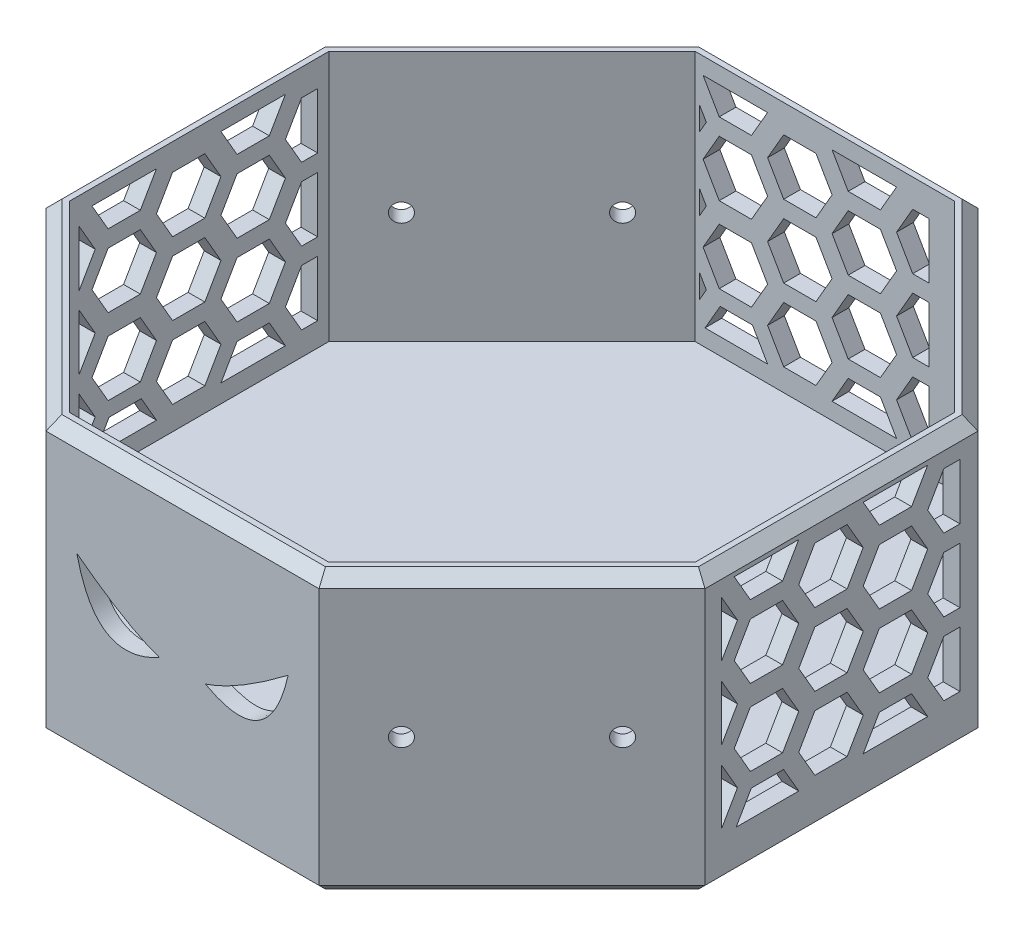
SolidWorks part; units mm, degrees
ref_plane "Plano frontal" through (0, 0, 0) normal (0, 0, 1) x (1, 0, 0)
ref_plane "Plano superior" through (0, 0, 0) normal (0, 1, 0) x (1, 0, 0)
ref_plane "Plano direito" through (0, 0, 0) normal (1, 0, 0) x (0, 0, -1)
sketch "Esboço1" plane through (0, 0, 0) normal (0, 1, 0) x (1, 0, 0)
  line L24 (59, -24.4386) -> (59, 24.4386)
  line L37 (24.4386, 59) -> (-24.4386, 59)
  line L38 (-24.4386, 59) -> (-59, 24.4386)
  line L39 (-59, 24.4386) -> (-59, -24.4386)
  line L40 (-59, -24.4386) -> (-24.4386, -59)
  line L41 (-24.4386, -59) -> (24.4386, -59)
  line L42 (24.4386, -59) -> (59, -24.4386)
  line L43 (59, 24.4386) -> (24.4386, 59)
  circle A0 centre (0, 0) radius 59 construction
  point P1 (-59, 0)
  dimension "D1" = 118
extrude "Ressalto-extrusão1" add sketch "Esboço1" along normal blind 50
sketch "Esboço2" plane through (0, 50, 0) normal (0, 1, 0) x (1, 0, 0)
  line L0 (59, 24.4386) -> (24.4386, 59) construction
  line L1 (56, 23.196) -> (23.196, 56)
  line L2 (23.196, 56) -> (-23.196, 56)
  line L3 (-23.196, 56) -> (-56, 23.196)
  line L4 (-56, 23.196) -> (-56, -23.196)
  line L5 (-56, -23.196) -> (-23.196, -56)
  line L6 (-23.196, -56) -> (23.196, -56)
  line L7 (23.196, -56) -> (56, -23.196)
  line L8 (56, -23.196) -> (56, 23.196)
  circle A0 centre (0, 0) radius 56 construction
  point P1 (-56, 0)
  dimension "D1" = 3
extrude "Corte-extrusão2" cut sketch "Esboço2" against normal blind 45
sketch "Esboço14" plane through (-41.7193, 0, 41.7193) normal (-0.7071, 0, 0.7071) x (0.7071, 0, 0.7071)
  line L0 (-14, 25) -> (14, 25) construction
  line L1 (-24.4386, 0) -> (24.4386, 0) construction
  circle A0 centre (-14, 25) radius 1.65
  circle A1 centre (14, 25) radius 1.65
  point P4 (0, 25)
  dimension "D3" = 3.3
  dimension "D1" = 28
  dimension "D2" = 25
extrude "Corte-extrusão6" cut sketch "Esboço14" against normal through all
sketch "Esboço15" plane through (-41.7193, 0, -41.7193) normal (-0.7071, 0, -0.7071) x (-0.7071, 0, 0.7071)
  line L0 (-14, 25) -> (14, 25) construction
  line L1 (-24.4386, 0) -> (24.4386, 0) construction
  circle A0 centre (-14, 25) radius 1.65
  circle A1 centre (14, 25) radius 1.65
  point P4 (0, 25)
  dimension "D1" = 3.3
  dimension "D2" = 28
  dimension "D3" = 25
extrude "Corte-extrusão7" cut sketch "Esboço15" against normal through all
chamfer "Chanfro1" distance 2 angle 45 16 edges at (-59, 0, 0) (-41.7193, 0, -41.7193) (0, 0, -59) (41.7193, 0, -41.7193) (59, 0, 0) (41.7193, 0, 41.7193) (0, 0, 59) (-41.7193, 0, 41.7193) (41.7193, 50, 41.7193) (59, 50, 0) (41.7193, 50, -41.7193) (0, 50, -59) (-41.7193, 50, -41.7193) (-59, 50, 0) (-41.7193, 50, 41.7193) (0, 50, 59)
sketch "Esboço11" plane through (-59, 0, 0) normal (-1, 0, 0) x (0, 0, 1)
  line L12 (18.862, 8.2396) -> (16.1485, 12.9395)
  line L15 (7.6615, 27.2396) -> (4.7748, 32.2396)
  line L53 (4.7748, 32.2396) -> (-0.9987, 32.2396)
  line L169 (-0.9987, 32.2396) -> (-3.8855, 27.2396)
  line L170 (16.1485, 12.9395) -> (10.375, 12.9395)
  line L171 (10.375, 12.9395) -> (7.6615, 8.2396)
  line L172 (-3.8855, 27.2396) -> (-0.9987, 22.2396)
  line L173 (-0.9987, 22.2396) -> (4.7748, 22.2396)
  line L174 (4.7748, 22.2396) -> (7.6615, 27.2396)
  line L175 (-3.8855, 21.2396) -> (-6.7722, 26.2396)
  line L176 (-6.7722, 26.2396) -> (-12.5457, 26.2396)
  line L177 (-12.5457, 26.2396) -> (-15.4325, 21.2396)
  line L178 (-15.4325, 21.2396) -> (-12.5457, 16.2396)
  line L179 (-12.5457, 16.2396) -> (-6.7722, 16.2396)
  line L180 (-6.7722, 16.2396) -> (-3.8855, 21.2396)
  line L181 (7.6615, 40.2396) -> (4.7748, 45.2396)
  line L182 (4.7748, 45.2396) -> (-0.9987, 45.2396)
  line L183 (-0.9987, 45.2396) -> (-3.8855, 40.2396)
  line L184 (-3.8855, 40.2396) -> (-0.9987, 35.2396)
  line L185 (-0.9987, 35.2396) -> (4.7748, 35.2396)
  line L186 (4.7748, 35.2396) -> (7.6615, 40.2396)
  line L187 (7.6615, 14.2396) -> (4.7748, 19.2396)
  line L188 (4.7748, 19.2396) -> (-0.9987, 19.2396)
  line L189 (-0.9987, 19.2396) -> (-3.8855, 14.2396)
  line L190 (-3.8855, 14.2396) -> (-0.9987, 9.2396)
  line L191 (-0.9987, 9.2396) -> (4.7748, 9.2396)
  line L192 (4.7748, 9.2396) -> (7.6615, 14.2396)
  line L193 (7.6615, 8.2396) -> (18.862, 8.2396)
  line L194 (-15.4325, 8.2396) -> (-3.8855, 8.2396)
  line L195 (-3.8855, 8.2396) -> (-6.7722, 13.2396)
  line L196 (-6.7722, 13.2396) -> (-12.5457, 13.2396)
  line L197 (-12.5457, 13.2396) -> (-15.4325, 8.2396)
  line L198 (-15.4325, 47.2396) -> (-3.8855, 47.2396)
  line L199 (-3.8855, 34.2396) -> (-6.7722, 39.2396)
  line L200 (-6.7722, 39.2396) -> (-12.5457, 39.2396)
  line L201 (-12.5457, 39.2396) -> (-15.4325, 34.2396)
  line L202 (-15.4325, 34.2396) -> (-12.5457, 29.2396)
  line L203 (-12.5457, 29.2396) -> (-6.7722, 29.2396)
  line L204 (-6.7722, 29.2396) -> (-3.8855, 34.2396)
  line L205 (-15.4325, 47.2396) -> (-12.5457, 42.2396)
  line L206 (-12.5457, 42.2396) -> (-6.7722, 42.2396)
  line L207 (-6.7722, 42.2396) -> (-3.8855, 47.2396)
  line L208 (-21.206, 45.2396) -> (-21.206, 9.2396) construction
  line L209 (-21.206, 45.2396) -> (-21.206, 35.2396)
  line L210 (-15.4325, 40.2396) -> (-18.3192, 45.2396)
  line L211 (-18.3192, 45.2396) -> (-21.206, 45.2396)
  line L212 (-21.206, 35.2396) -> (-18.3192, 35.2396)
  line L213 (-18.3192, 35.2396) -> (-15.4325, 40.2396)
  line L214 (-15.4325, 27.2396) -> (-18.3192, 32.2396)
  line L215 (-18.3192, 32.2396) -> (-21.206, 32.2396)
  line L216 (-21.206, 32.2396) -> (-21.206, 22.2396)
  line L217 (-21.206, 22.2396) -> (-18.3192, 22.2396)
  line L218 (-18.3192, 22.2396) -> (-15.4325, 27.2396)
  line L219 (-15.4325, 14.2396) -> (-18.3192, 19.2396)
  line L220 (-18.3192, 19.2396) -> (-21.206, 19.2396)
  line L221 (-21.206, 19.2396) -> (-21.206, 9.2396)
  line L222 (-21.206, 9.2396) -> (-18.3192, 9.2396)
  line L223 (-18.3192, 9.2396) -> (-15.4325, 14.2396)
  line L224 (19.2085, 34.2396) -> (16.3218, 39.2396)
  line L225 (16.3218, 39.2396) -> (10.5483, 39.2396)
  line L226 (10.5483, 39.2396) -> (7.6615, 34.2396)
  line L227 (7.6615, 34.2396) -> (10.5483, 29.2396)
  line L228 (10.5483, 29.2396) -> (16.3218, 29.2396)
  line L229 (16.3218, 29.2396) -> (19.2085, 34.2396)
  line L230 (7.6615, 47.2396) -> (10.5483, 42.2396)
  line L231 (10.5483, 42.2396) -> (16.3218, 42.2396)
  line L232 (16.3218, 42.2396) -> (19.2085, 47.2396)
  line L233 (7.6615, 47.2396) -> (19.2085, 47.2396)
  line L234 (21.5179, 45.2396) -> (21.5179, 35.2396)
  line L235 (19.2085, 20.6028) -> (16.3218, 25.6028)
  line L236 (16.3218, 25.6028) -> (10.5483, 25.6028)
  line L237 (10.5483, 25.6028) -> (7.6615, 20.6028)
  line L238 (7.6615, 20.6028) -> (10.5483, 15.6028)
  line L239 (10.5483, 15.6028) -> (16.3218, 15.6028)
  line L240 (16.3218, 15.6028) -> (19.2085, 20.6028)
  line L241 (21.5179, 45.2396) -> (18.6312, 40.2396)
  line L242 (18.6312, 40.2396) -> (21.5179, 35.2396)
  line L243 (21.5179, 45.2396) -> (21.5179, 8.2396) construction
  line L244 (21.5179, 32.2396) -> (21.5179, 22.2396)
  line L245 (18.6312, 27.2396) -> (21.5179, 22.2396)
  line L246 (21.5179, 32.2396) -> (18.6312, 27.2396)
  line L247 (21.5179, 19.2396) -> (21.5179, 9.2396)
  line L248 (18.6312, 14.2396) -> (21.5179, 9.2396)
  line L249 (21.5179, 19.2396) -> (18.6312, 14.2396)
  arc A0 (18.2528, 8.2396) -> (8.2708, 8.2396) centre (13.2618, 7.9395) ccw construction
  circle A2 centre (1.888, 27.2396) radius 5 construction
  circle A3 centre (-9.659, 21.2396) radius 5 construction
  circle A4 centre (1.888, 40.2396) radius 5 construction
  circle A5 centre (1.888, 14.2396) radius 5 construction
  arc A6 (-4.659, 8.2396) -> (-14.659, 8.2396) centre (-9.659, 8.2396) ccw construction
  circle A7 centre (-9.659, 34.2396) radius 5 construction
  arc A8 (-14.659, 47.2396) -> (-4.659, 47.2396) centre (-9.659, 47.2396) ccw construction
  arc A9 (-21.206, 35.2396) -> (-21.206, 45.2396) centre (-21.206, 40.2396) ccw construction
  circle A10 centre (13.435, 34.2396) radius 5 construction
  arc A11 (8.435, 47.2396) -> (18.435, 47.2396) centre (13.435, 47.2396) ccw construction
  circle A12 centre (13.435, 20.6028) radius 5 construction
  arc A13 (21.5179, 44.3221) -> (21.5179, 36.1571) centre (24.4047, 40.2396) ccw construction
  point P52 (13.2618, 8.2396)
  dimension "D1" = 10
  dimension "D2" = 10
  dimension "D3" = 10
  dimension "D4" = 10
  dimension "D6" = 10
  dimension "D9" = 10
  dimension "D12" = 10
  dimension "D15" = 10
  dimension "D5" = 3
  dimension "D7" = 3
  dimension "D8" = 3
  dimension "D10" = 3
  dimension "D11" = 3
  dimension "D13" = 3
  dimension "D14" = 3
  dimension "D16" = 3
  dimension "D17" = 3
  dimension "D18" = 3
  dimension "D19" = 3
extrude "Corte-extrusão3" cut sketch "Esboço11" against normal through all
sketch "Esboço12" plane through (0, 0, -59) normal (0, 0, -1) x (-1, 0, 0)
  line L0 (24.4386, 48) -> (-24.4386, 48) construction
  line L1 (-24.4386, 2) -> (24.4386, 2) construction
  line L2 (24.4386, 48) -> (24.4386, 2) construction
  line L3 (21.4386, 8) -> (18.7251, 12.6999)
  line L4 (10.2381, 27) -> (7.3513, 32)
  line L5 (7.3513, 32) -> (1.5778, 32)
  line L6 (1.5778, 32) -> (-1.3089, 27)
  line L127 (18.7251, 12.6999) -> (12.9516, 12.6999)
  line L128 (12.9516, 12.6999) -> (10.2381, 8)
  line L132 (-1.3089, 27) -> (1.5778, 22)
  line L133 (1.5778, 22) -> (7.3513, 22)
  line L134 (7.3513, 22) -> (10.2381, 27)
  line L135 (-1.3089, 21) -> (-4.1957, 26)
  line L136 (-4.1957, 26) -> (-9.9692, 26)
  line L137 (-9.9692, 26) -> (-12.8559, 21)
  line L138 (-12.8559, 21) -> (-9.9692, 16)
  line L139 (-9.9692, 16) -> (-4.1957, 16)
  line L140 (-4.1957, 16) -> (-1.3089, 21)
  line L147 (10.2381, 40) -> (7.3513, 45)
  line L148 (7.3513, 45) -> (1.5778, 45)
  line L149 (1.5778, 45) -> (-1.3089, 40)
  line L150 (-1.3089, 40) -> (1.5778, 35)
  line L151 (1.5778, 35) -> (7.3513, 35)
  line L152 (7.3513, 35) -> (10.2381, 40)
  line L153 (10.2381, 14) -> (7.3513, 19)
  line L154 (7.3513, 19) -> (1.5778, 19)
  line L155 (1.5778, 19) -> (-1.3089, 14)
  line L156 (-1.3089, 14) -> (1.5778, 9)
  line L157 (1.5778, 9) -> (7.3513, 9)
  line L158 (7.3513, 9) -> (10.2381, 14)
  line L159 (10.2381, 8) -> (21.4386, 8)
  line L160 (-12.8559, 8) -> (-1.3089, 8)
  line L161 (15.8383, 2.6999) -> (18.7251, 2.6999) [skipped]
  line L162 (20.1685, 5.1999) -> (21.6119, 7.6999) [skipped]
  line L163 (10.0648, 7.6999) -> (12.9516, 2.6999) [skipped]
  line L164 (-1.3089, 8) -> (-4.1957, 13)
  line L165 (-4.1957, 13) -> (-9.9692, 13)
  line L166 (-9.9692, 13) -> (-12.8559, 8)
  line L170 (-12.8559, 47) -> (-1.3089, 47)
  line L171 (-1.7042, 7.3154) -> (-0.2608, 9.8154) [skipped]
  line L172 (-9.9692, 3) -> (-7.0824, 3) [skipped]
  line L173 (-12.8559, 8) -> (-11.4125, 5.5) [skipped]
  line L174 (-1.3089, 34) -> (-4.1957, 39)
  line L175 (-4.1957, 39) -> (-9.9692, 39)
  line L176 (-9.9692, 39) -> (-12.8559, 34)
  line L177 (-12.8559, 34) -> (-9.9692, 29)
  line L178 (-9.9692, 29) -> (-4.1957, 29)
  line L179 (-4.1957, 29) -> (-1.3089, 34)
  line L183 (-12.8559, 47) -> (-9.9692, 42)
  line L184 (-9.9692, 42) -> (-4.1957, 42)
  line L185 (-4.1957, 42) -> (-1.3089, 47)
  line L186 (-18.6294, 45) -> (-18.6294, 9) construction
  line L187 (-7.0824, 52) -> (-9.9692, 52) [skipped]
  line L188 (-11.4125, 49.5) -> (-12.8559, 47) [skipped]
  line L189 (-2.7523, 49.5) -> (-4.1957, 52) [skipped]
  line L190 (-18.6294, 45) -> (-18.6294, 35)
  line L191 (-12.8559, 40) -> (-15.7427, 45)
  line L192 (-15.7427, 45) -> (-18.6294, 45)
  line L195 (-18.6294, 35) -> (-15.7427, 35)
  line L196 (-15.7427, 35) -> (-12.8559, 40)
  line L197 (-12.8559, 27) -> (-15.7427, 32)
  line L198 (-23.1667, 42.1413) -> (-24.61, 39.6413) [skipped]
  line L199 (-23.1667, 37.8587) -> (-21.7233, 35.3587) [skipped]
  line L200 (-15.7427, 32) -> (-18.6294, 32)
  line L201 (-18.6294, 32) -> (-18.6294, 22)
  line L202 (-18.6294, 22) -> (-15.7427, 22)
  line L203 (-15.7427, 22) -> (-12.8559, 27)
  line L204 (-12.8559, 14) -> (-15.7427, 19)
  line L205 (-15.7427, 19) -> (-18.6294, 19)
  line L206 (-18.6294, 19) -> (-18.6294, 9)
  line L207 (-18.6294, 9) -> (-15.7427, 9)
  line L208 (-15.7427, 9) -> (-12.8559, 14)
  line L210 (21.7851, 34) -> (18.8983, 39)
  line L211 (18.8983, 39) -> (13.1248, 39)
  line L212 (13.1248, 39) -> (10.2381, 34)
  line L213 (10.2381, 34) -> (13.1248, 29)
  line L214 (13.1248, 29) -> (18.8983, 29)
  line L215 (18.8983, 29) -> (21.7851, 34)
  line L220 (10.2381, 47) -> (13.1248, 42)
  line L221 (13.1248, 42) -> (18.8983, 42)
  line L222 (18.8983, 42) -> (21.7851, 47)
  line L223 (10.2381, 47) -> (21.7851, 47)
  line L224 (22.4376, 42.1302) -> (22.4376, 37.8698)
  line L225 (15.1832, 52) -> (12.2964, 52) [skipped]
  line L226 (11.4744, 49.1413) -> (10.031, 46.6413) [skipped]
  line L227 (20.1346, 49.8587) -> (18.6912, 52.3587) [skipped]
  line L228 (21.7851, 20.3632) -> (18.8983, 25.3632)
  line L229 (18.8983, 25.3632) -> (13.1248, 25.3632)
  line L230 (13.1248, 25.3632) -> (10.2381, 20.3632)
  line L231 (10.2381, 20.3632) -> (13.1248, 15.3632)
  line L232 (13.1248, 15.3632) -> (18.8983, 15.3632)
  line L233 (18.8983, 15.3632) -> (21.7851, 20.3632)
  line L236 (22.4376, 42.1302) -> (21.2078, 40)
  line L237 (21.2078, 40) -> (22.4376, 37.8698)
  line L240 (22.4376, 42.1302) -> (22.4376, 8) construction
  line L241 (30.6825, 37.8497) -> (29.2392, 40.3497) [skipped]
  line L242 (26.1412, 34.2846) -> (27.5846, 36.7846) [skipped]
  line L243 (20.7831, 36.4349) -> (23.6699, 36.4349) [skipped]
  line L244 (28.8301, 43.5651) -> (25.9433, 43.5651) [skipped]
  line L245 (22.4376, 29.1302) -> (22.4376, 24.8698)
  line L246 (21.2078, 27) -> (22.4376, 24.8698)
  line L247 (22.4376, 29.1302) -> (21.2078, 27)
  line L248 (22.4376, 16.1302) -> (22.4376, 11.8698)
  line L249 (21.2078, 14) -> (22.4376, 11.8698)
  line L250 (22.4376, 16.1302) -> (21.2078, 14)
  arc A0 (20.8293, 8) -> (10.8474, 8) centre (15.8383, 7.6999) ccw construction
  circle A1 centre (4.4646, 27) radius 5 construction
  circle A2 centre (-7.0824, 21) radius 5 construction
  circle A3 centre (4.4646, 40) radius 5 construction
  circle A4 centre (4.4646, 14) radius 5 construction
  arc A5 (-2.0824, 8) -> (-12.0824, 8) centre (-7.0824, 8) ccw construction
  circle A6 centre (-7.0824, 34) radius 5 construction
  arc A7 (-12.0824, 47) -> (-2.0824, 47) centre (-7.0824, 47) ccw construction
  arc A8 (-18.6294, 35) -> (-18.6294, 45) centre (-18.6294, 40) ccw construction
  circle A9 centre (16.0116, 34) radius 5 construction
  arc A10 (11.0116, 47) -> (21.0116, 47) centre (16.0116, 47) ccw construction
  circle A11 centre (16.0116, 20.3632) radius 5 construction
  arc A12 (22.4376, 44.0825) -> (22.4376, 35.9175) centre (25.3244, 40) ccw construction
  point P63 (15.8383, 8)
  dimension "D3" = 3
  dimension "D2" = 10
  dimension "D4" = 10
  dimension "D6" = 10
  dimension "D8" = 10
  dimension "D10" = 10
  dimension "D13" = 10
  dimension "D16" = 10
  dimension "D19" = 10
  dimension "D20" = 3
  dimension "D5" = 3
  dimension "D7" = 3
  dimension "D9" = 3
  dimension "D11" = 3
  dimension "D12" = 3
  dimension "D14" = 6
  dimension "D15" = 3
  dimension "D17" = 3
  dimension "D18" = 3
  dimension "D22" = 3
  dimension "D23" = 3
  dimension "D24" = 3
  dimension "D21" = 3
  dimension "D25" = 3
extrude "Corte-extrusão4" cut sketch "Esboço12" against normal blind 10
sketch "Esboço13" plane through (0, 0, 59) normal (0, 0, 1) x (1, 0, 0)
  line L0 (0, 2) -> (0, 48) construction
  line L1 (-24.4386, 2) -> (24.4386, 2) construction
  line L2 (24.4386, 48) -> (-24.4386, 48) construction
  spline S0 degree 2 poles (-18.9179, 31.8128) (-9.7909, 24.9037) (-4.1074, 23.0506) knots 0 0 0 1 1 1
  spline S1 degree 2 poles (-18.9179, 31.8128) (-15.5168, 16.8069) (-4.1074, 23.0506) knots 0 0 0 1 1 1
  spline S2 degree 2 poles (18.9179, 31.8128) (9.7909, 24.9037) (4.1074, 23.0506) knots 0 0 0 1 1 1
  spline S3 degree 2 poles (18.9179, 31.8128) (15.5168, 16.8069) (4.1074, 23.0506) knots 0 0 0 1 1 1
extrude "Corte-extrusão5" cut sketch "Esboço13" against normal blind 10
